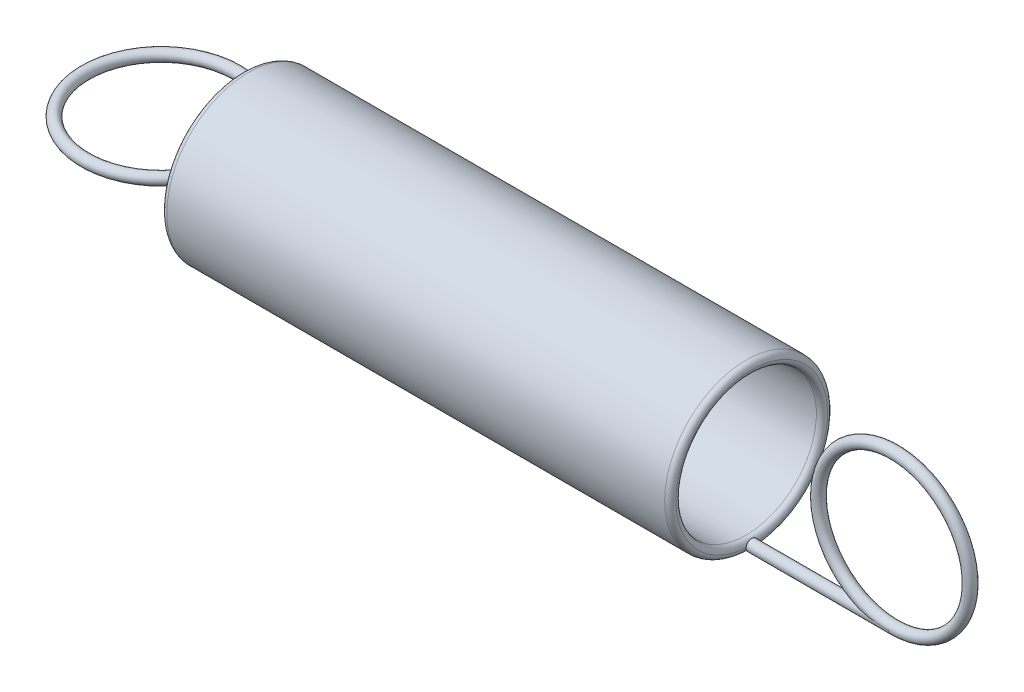
SolidWorks part; units mm, degrees
ref_plane "Front Plane" through (0, 0, 0) normal (0, 0, 1) x (1, 0, 0)
ref_plane "Top Plane" through (0, 0, 0) normal (0, 1, 0) x (1, 0, 0)
ref_plane "Right Plane" through (0, 0, 0) normal (1, 0, 0) x (0, 0, -1)
sketch "Sketch1" plane through (0, 0, 0) normal (0, 1, 0) x (1, 0, 0)
  line L0 (8, 0) -> (33, 0) construction
  line L1 (8, 4) -> (33, 4)
  line L2 (8, 4) -> (8, -4)
  line L3 (8, -4) -> (33, -4)
  line L4 (33, 4) -> (33, -4)
  line L5 (33, 0) -> (44, 0)
  line L6 (0, 0) -> (4, 0) construction
  circle A0 centre (4, 0) radius 4
  circle A1 centre (4, 0) radius 3.45
  dimension "D1" = 8
  dimension "D2" = 6.9
  dimension "D3" = 44
  dimension "D4" = 11
sketch "Sketch2" plane through (0, 0, 0) normal (0, 0, 1) x (1, 0, 0)
  line L0 (8, 0) -> (0, 0) construction
  line L1 (4, 0) -> (4, 1.1131) construction
  circle A0 centre (0.275, 0) radius 0.275
  dimension "D1" = 0.55
revolve "Revolve1" add sketch "Sketch2" angle 360 about L1
sketch "Sketch3" plane through (0, 0, 0) normal (0, 0, 1) x (1, 0, 0)
  line L0 (8, 0) -> (33, 0) construction
  line L1 (8, 0) -> (33, 0) construction
  line L2 (8, 0) -> (8, 4) construction
  line L3 (8, 4) -> (33, 4)
  line L4 (33, 0) -> (33, 4) construction
  line L5 (33, 0) -> (44, 0) construction
  line L6 (8, 4) -> (8, 3.45)
  line L7 (8, 3.45) -> (33, 3.45)
  line L8 (33, 3.45) -> (33, 4)
  line L9 (8, 0) -> (4, 0) construction
  line L10 (7.45, 0) -> (0.55, 0) construction
  arc A0 (7.725, -0.275) -> (7.725, 0.275) centre (7.725, 0) ccw construction
  dimension "D2" = 0.55
revolve "Revolve2" add sketch "Sketch3" angle 360 about L1
fillet "Fillet1" radius 0.275 4 edges at (8, 0, 3.45) (8, 0, 4) (33, 0, 3.45) (33, 0, 4)
ref_plane "Plane1" through (33, 0, 0) normal (1, 0, 0) x (0, 0, -1)
sketch "Sketch4" plane through (33, 0, 0) normal (1, 0, 0) x (0, 0, -1)
  line L0 (0, 0) -> (0, -3.725) construction
  circle A0 centre (0, -3.725) radius 0.275
  circle A2 centre (0, 0) radius 3.725 construction
  circle A3 centre (0, 0) radius 3.45 construction
  point P2 (0.0102, -3.725)
extrude "Boss-Extrude1" add sketch "Sketch4" along normal blind 7 separate body
sketch "Sketch5" plane through (40, 0, 0) normal (1, 0, 0) x (0, 0, -1)
  line L0 (0, 0) -> (4, 0) construction
  line L1 (3.45, 0) -> (-3.45, 0) construction
  circle A0 centre (0, 0) radius 4 construction
  circle A1 centre (0, -3.725) radius 0.275
  circle A2 centre (0, -3.725) radius 0.275
  dimension "D1" = 0
revolve "Revolve3" add sketch "Sketch5" angle 360 about L0
